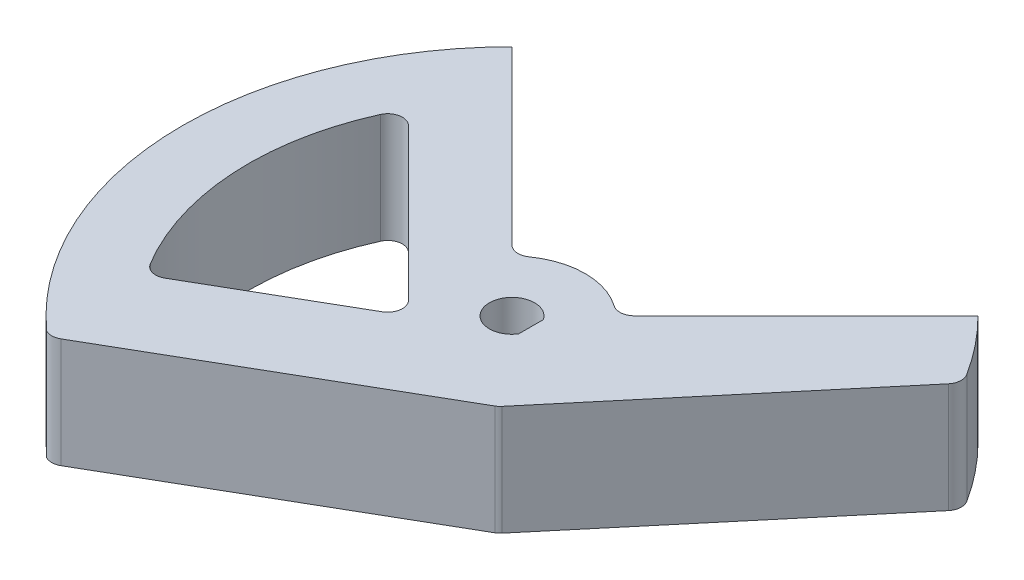
SolidWorks part; units mm, degrees
material "ABS"
ref_plane "Front Plane" through (0, 0, 0) normal (0, 0, 1) x (1, 0, 0)
ref_plane "Top Plane" through (0, 0, 0) normal (0, 1, 0) x (1, 0, 0)
ref_plane "Right Plane" through (0, 0, 0) normal (1, 0, 0) x (0, 0, -1)
sketch "Sketch1" plane through (0, 0, 0) normal (0, 1, 0) x (1, 0, 0)
  line L0 (-31.8198, 31.8198) -> (-7.0711, 7.0711)
  line L1 (7.0711, 7.0711) -> (31.8198, 31.8198)
  line L2 (0, 0) -> (0, 20) construction
  line L3 (0, 0) -> (-7.0711, 7.0711) construction
  line L4 (7.0711, 7.0711) -> (0, 0) construction
  arc A0 (-31.8198, 31.8198) -> (31.8198, 31.8198) centre (0, 0) ccw
  circle A1 centre (0, 0) radius 3
  arc A2 (7.0711, 7.0711) -> (-7.0711, 7.0711) centre (0, 0) ccw
  dimension "D1" = 6
  dimension "D2" = 90
  dimension "D3" = 20
  dimension "D4" = 45
extrude "Boss-Extrude1" add sketch "Sketch1" along normal blind 15
sketch "Sketch2" plane through (0, 15, 0) normal (0, 1, 0) x (1, 0, 0)
  line L0 (2.5, 1.6583) -> (2.5, -1.6583)
  line L1 (-3, 0) -> (-3, -6.6376) construction
  arc A0 (2.5, -1.6583) -> (2.5, 1.6583) centre (0, 0) ccw
  circle A1 centre (0, 0) radius 3 construction
  dimension "D1" = 5.5
extrude "Shaft D" add sketch "Sketch2" against normal up to surface (15 mm away) up to face at (0, 0, -0.9727)
sketch "Sketch3" plane through (0, 15, 0) normal (0, 1, 0) x (1, 0, 0)
  line L0 (-31.8198, 31.8198) -> (-27.5772, 36.0624)
  line L1 (-27.5772, 36.0624) -> (-27.5772, 27.5772)
  line L2 (-7.0711, 7.0711) -> (-31.8198, 31.8198) construction
  line L3 (-27.5772, 27.5772) -> (-31.8198, 31.8198)
  line L4 (0, 0) -> (0, 30.6174) construction
  line L5 (27.5772, 27.5772) -> (31.8198, 31.8198)
  line L6 (27.5772, 36.0624) -> (27.5772, 27.5772)
  line L7 (31.8198, 31.8198) -> (27.5772, 36.0624)
  dimension "D1" = 6
extrude "Boss-Extrude2" [suppressed] add sketch "Sketch3" against normal up to surface (15 mm away) up to face at (0, 0, -0.9727)
sketch "Sketch5" plane through (0, 15, 0) normal (0, 1, 0) x (1, 0, 0)
  line L0 (31.8198, 31.8198) -> (0, 0) construction
  line L1 (0, 0) -> (-31.8198, 31.8198) construction
  line L2 (-31.8198, 31.8198) -> (31.8198, 31.8198) construction
sketch "Sketch4" plane through (0, 15, 0) normal (0, 1, 0) x (1, 0, 0)
  line L0 (-148.943, 0) -> (142.5774, 0) construction
  line L1 (0, 0) -> (-107.5774, -62.1099) construction
  line L2 (0, 0) -> (96.6052, -81.0614) construction
  line L8 (0, 0) -> (81.0614, 96.6052) construction
  line L9 (0, 0) -> (62.1099, -107.5774) construction
  line L10 (-107.5774, -62.1099) -> (62.1099, -107.5774) construction
  line L11 (81.0614, 96.6052) -> (96.6052, -81.0614) construction
  line L14 (11.4907, -9.6418) -> (45.5038, 30.8934)
  line L15 (11.4907, -9.6418) -> (-38.9929, -38.7885)
  arc A2 (-38.9929, -38.7885) -> (45.5038, 30.8934) centre (0, 0) ccw
  dimension "D4" = 55
  dimension "D1" = 40
  dimension "D3" = 30
  dimension "D5" = 15
extrude "Cut-Extrude1" cut sketch "Sketch4" against normal through all
sketch "Sketch6" plane through (7.0477, 0, 12.207) normal (0.5, 0, 0.866) x (0.866, 0, -0.5)
  line L0 (5.1303, 0) -> (-42.7355, 0) construction
  line L1 (-42.7355, 15) -> (5.1303, 15)
  line L2 (-42.7355, 15) -> (-42.7355, 0)
  line L3 (-42.7355, 0) -> (5.1303, 0)
  line L4 (5.1303, 15) -> (5.1303, 0)
  line L5 (-42.7355, 15) -> (5.1303, 0) construction
  line L6 (-42.7355, 0) -> (5.1303, 15) construction
  point P4 (-18.8026, 7.5)
extrude "Boss-Extrude3" add sketch "Sketch6" along normal blind 0.9
sketch "Sketch7" plane through (0, 15, 0) normal (0, 1, 0) x (1, 0, 0)
  line L0 (-31.5251, 17.383) -> (-7.0711, -7.0711)
  line L1 (-7.0711, -7.0711) -> (-29.8021, -20.1949)
  line L2 (11.9407, -10.4212) -> (-29.5123, -34.3541) construction
  line L3 (-7.0711, 7.0711) -> (-31.8198, 31.8198) construction
  arc A0 (-31.5251, 17.383) -> (-29.8021, -20.1949) centre (0, 0) ccw
  dimension "D1" = 36
  dimension "D3" = 10
  dimension "D4" = 12.4072
extrude "Cut-Extrude2" cut sketch "Sketch7" against normal through all contours L0 L1 A0
sketch "Sketch9" plane through (0, 15, 0) normal (0, 1, 0) x (1, 0, 0)
  line L0 (2.5, 1.6583) -> (2.5, -1.6583) construction
  line L1 (2.59, 1.6852) -> (2.59, -1.6852)
  arc A0 (2.5, 1.6583) -> (2.5, -1.6583) centre (0, 0) ccw construction
  arc A1 (2.59, 1.6852) -> (2.59, -1.6852) centre (0, 0) ccw
  dimension "D1" = 0.09
extrude "Shaft Hole Expansion" cut sketch "Sketch9" against normal through all
sketch "Sketch10" plane through (0, 15, 0) normal (0, 1, 0) x (1, 0, 0)
  line L0 (11.4907, -9.6418) -> (7.4934, -14.4056)
  line L1 (7.4934, -14.4056) -> (21.6668, -15.2895)
  line L2 (21.6668, -15.2895) -> (11.4907, -9.6418)
  line L3 (38.7618, 22.8587) -> (11.4907, -9.6418) construction
  line L4 (11.4907, -9.6418) -> (13.8307, -6.8531) construction
extrude "Cut-Extrude4" cut sketch "Sketch10" against normal through all
fillet "Fillet1" radius 2 8 edges at (-29.8021, 7.5, 20.1949) (-31.5251, 7.5, -17.383) (-7.0711, 7.5, 7.0711) (-7.0711, 7.5, -7.0711) (7.0711, 7.5, -7.0711) (-29.5123, 7.5, 34.3541) (9.7992, 7.5, 11.6576) (38.7618, 7.5, -22.8587)
